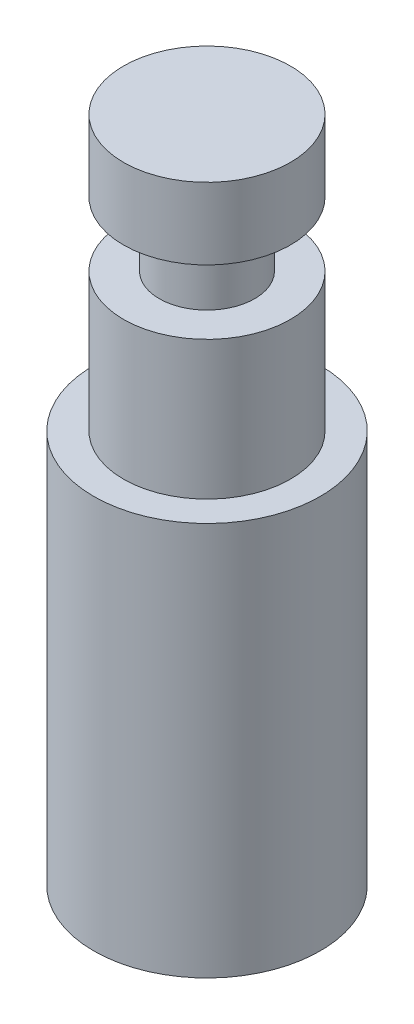
SolidWorks part; units mm, degrees
ref_plane "Front Plane" through (0, 0, 0) normal (0, 0, 1) x (1, 0, 0)
ref_plane "Top Plane" through (0, 0, 0) normal (0, 1, 0) x (1, 0, 0)
ref_plane "Right Plane" through (0, 0, 0) normal (1, 0, 0) x (0, 0, -1)
sketch "Sketch1" plane through (0, 0, 0) normal (0, 1, 0) x (1, 0, 0)
  circle A0 centre (0, 0) radius 4.75
  dimension "D1" = 9.5
extrude "Boss-Extrude1" add sketch "Sketch1" along normal blind 28
sketch "Sketch2" plane through (0, 28, 0) normal (0, 1, 0) x (1, 0, 0)
  circle A0 centre (0, 0) radius 3.5
  dimension "D1" = 7
extrude "Cut-Extrude1" cut sketch "Sketch2" against normal blind 11.5 flip side to cut
sketch "Sketch3" plane through (0, 28, 0) normal (0, 1, 0) x (1, 0, 0)
  circle A0 centre (0, 0) radius 2
  dimension "D1" = 4
extrude "Cut-Extrude2" cut sketch "Sketch3" against normal blind 2.7 from offset 3 flip side to cut offset against normal yes
